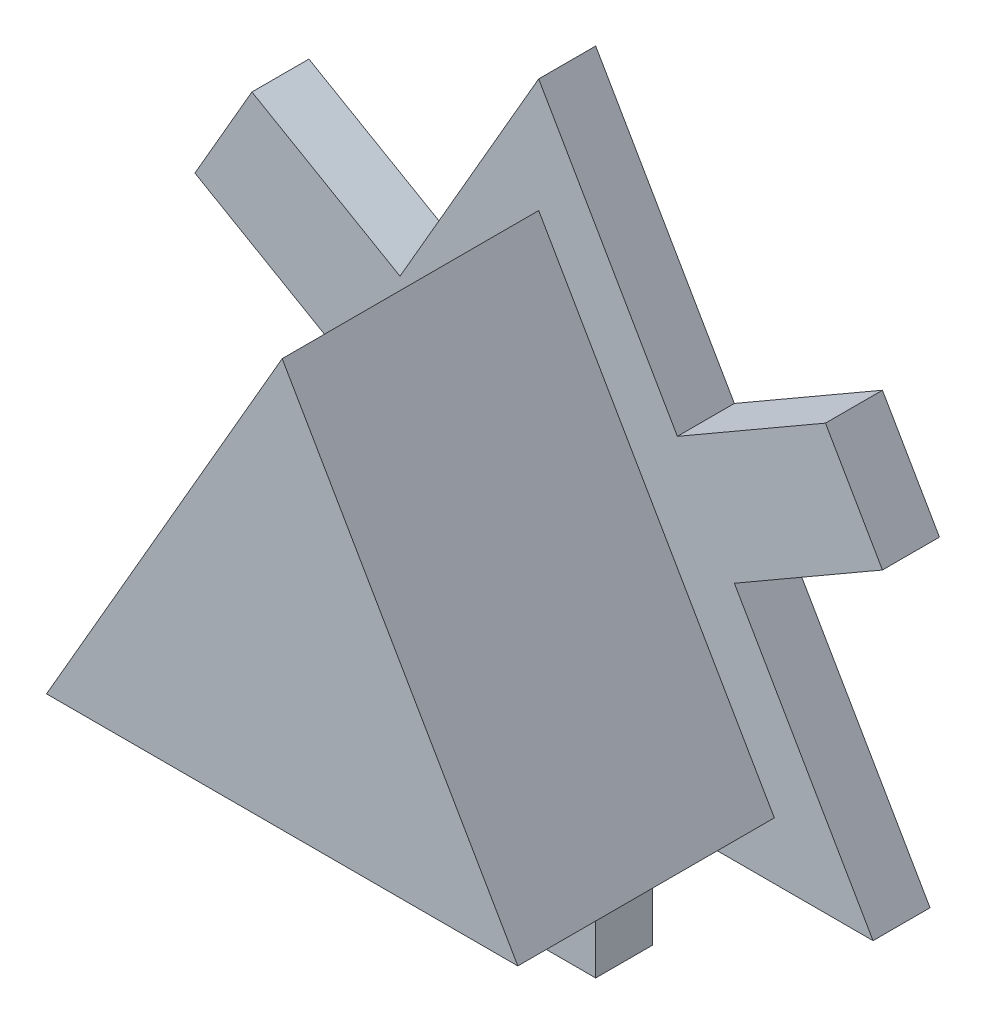
SolidWorks part; units mm, degrees
ref_plane "Front Plane" through (0, 0, 0) normal (0, 0, 1) x (1, 0, 0)
ref_plane "Top Plane" through (0, 0, 0) normal (0, 1, 0) x (1, 0, 0)
ref_plane "Right Plane" through (0, 0, 0) normal (1, 0, 0) x (0, 0, -1)
sketch "Sketch1" plane through (0, 0, 0) normal (0, 0, 1) x (1, 0, 0)
  line L9 (4.3792, -1.2984) -> (12.6472, -1.2984)
  line L10 (8.5132, 5.8619) -> (4.3792, -1.2984)
  line L11 (12.6472, -1.2984) -> (8.5132, 5.8619)
  line L12 (4.3792, -1.2984) -> (12.6472, -1.2984)
  line L13 (8.5132, 5.8619) -> (4.3792, -1.2984)
  line L14 (12.6472, -1.2984) -> (8.5132, 5.8619)
  circle A0 centre (8.5132, 1.0884) radius 2.3868 construction
  dimension "D1" = 0.5
extrude "Boss-Extrude1" add sketch "Sketch1" along normal blind 4.5
sketch "Sketch2" plane through (0, 0, 0) normal (0, 0, -1) x (-1, 0, 0)
  line L36 (-14.5443, 3.4157) -> (-11.9462, 1.9157)
  line L37 (-11.9462, 1.9157) -> (-14.3792, -2.2984)
  line L38 (-14.3792, -2.2984) -> (-9.5132, -2.2984)
  line L39 (-9.5132, -2.2984) -> (-9.5132, -5.2984)
  line L40 (-9.5132, -5.2984) -> (-7.5132, -5.2984)
  line L41 (-7.5132, -5.2984) -> (-7.5132, -2.2984)
  line L42 (-7.5132, -2.2984) -> (-2.6472, -2.2984)
  line L43 (-2.6472, -2.2984) -> (-5.0802, 1.9157)
  line L44 (-5.0802, 1.9157) -> (-2.4821, 3.4157)
  line L45 (-2.4821, 3.4157) -> (-3.4821, 5.1478)
  line L46 (-3.4821, 5.1478) -> (-6.0802, 3.6478)
  line L47 (-6.0802, 3.6478) -> (-8.5132, 7.8619)
  line L48 (-8.5132, 7.8619) -> (-10.9462, 3.6478)
  line L49 (-10.9462, 3.6478) -> (-13.5443, 5.1478)
  line L50 (-13.5443, 5.1478) -> (-14.5443, 3.4157)
  line L51 (-14.5443, 3.4157) -> (-11.9462, 1.9157)
  line L52 (-11.9462, 1.9157) -> (-14.3792, -2.2984)
  line L53 (-14.3792, -2.2984) -> (-9.5132, -2.2984)
  line L54 (-9.5132, -2.2984) -> (-9.5132, -5.2984)
  line L55 (-9.5132, -5.2984) -> (-7.5132, -5.2984)
  line L56 (-7.5132, -5.2984) -> (-7.5132, -2.2984)
  line L57 (-7.5132, -2.2984) -> (-2.6472, -2.2984)
  line L58 (-2.6472, -2.2984) -> (-5.0802, 1.9157)
  line L59 (-5.0802, 1.9157) -> (-2.4821, 3.4157)
  line L60 (-2.4821, 3.4157) -> (-3.4821, 5.1478)
  line L61 (-3.4821, 5.1478) -> (-6.0802, 3.6478)
  line L62 (-6.0802, 3.6478) -> (-8.5132, 7.8619)
  line L63 (-8.5132, 7.8619) -> (-10.9462, 3.6478)
  line L64 (-10.9462, 3.6478) -> (-13.5443, 5.1478)
  line L65 (-13.5443, 5.1478) -> (-14.5443, 3.4157)
  dimension "D1" = 0.5
extrude "Boss-Extrude2" add sketch "Sketch2" along normal blind 1
